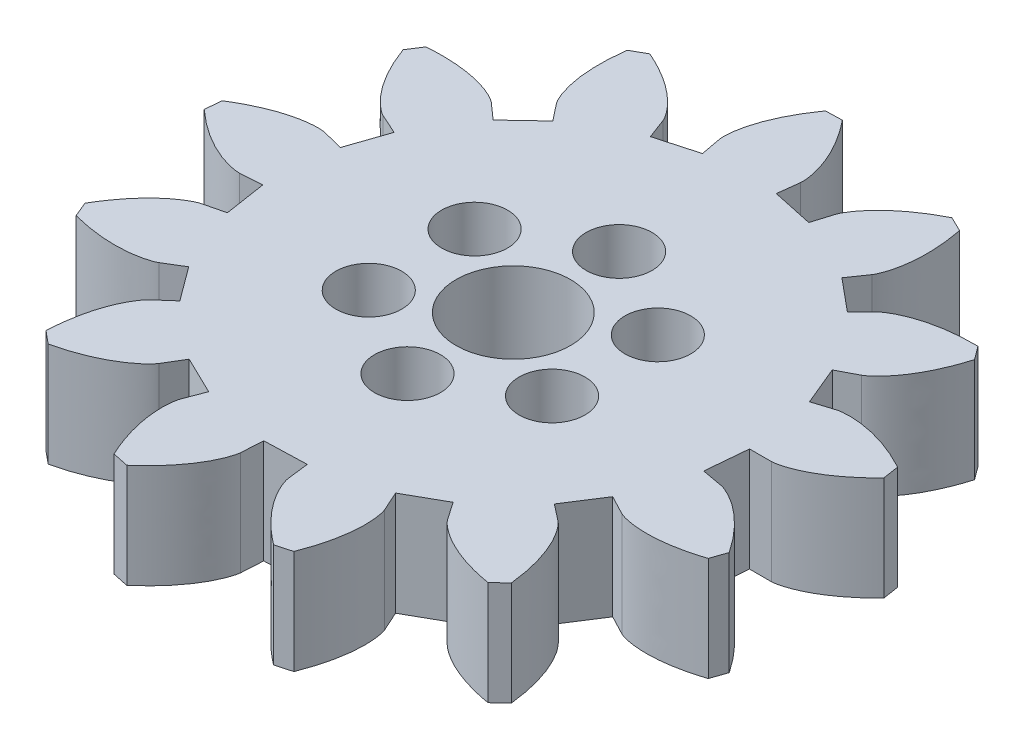
SolidWorks part; units mm, degrees
ref_plane "Front Plane" through (0, 0, 0) normal (0, 0, 1) x (1, 0, 0)
ref_plane "Top Plane" through (0, 0, 0) normal (0, 1, 0) x (1, 0, 0)
ref_plane "Right Plane" through (0, 0, 0) normal (1, 0, 0) x (0, 0, -1)
sketch "Sketch1" plane through (0, 0, 0) normal (0, 1, 0) x (1, 0, 0)
  circle A0 centre (0, 0) radius 8.2743 construction
  circle A1 centre (0, 0) radius 8.2743
  circle A3 centre (-2.6414, -1.525) radius 0.95
  circle A4 centre (-2.6414, -1.525) radius 0.95
  circle A5 centre (0, -3.05) radius 0.95
  circle A6 centre (0, -3.05) radius 0.95
  circle A7 centre (2.6414, -1.525) radius 0.95
  circle A8 centre (2.6414, -1.525) radius 0.95
  circle A9 centre (2.6414, 1.525) radius 0.95
  circle A10 centre (2.6414, 1.525) radius 0.95
  circle A11 centre (0, 3.05) radius 0.95
  circle A12 centre (0, 3.05) radius 0.95
  circle A13 centre (-2.6414, 1.525) radius 0.95
  circle A14 centre (-2.6414, 1.525) radius 0.95
  dimension "D1" = 0
  dimension "D2" = 0
  dimension "D3" = 0
  dimension "D4" = 0
  dimension "D5" = 0
  dimension "D6" = 0
sketch "Sketch2" plane through (0, 0, 0) normal (0, 1, 0) x (1, 0, 0)
  line L0 (6.8098, 0) -> (7.4374, 0)
  line L1 (7.4374, 0) -> (7.4435, 0.0002)
  line L2 (7.4435, 0.0002) -> (7.455, 0.0009)
  line L3 (7.455, 0.0009) -> (7.4719, 0.0023)
  line L4 (7.4719, 0.0023) -> (7.494, 0.0048)
  line L5 (7.494, 0.0048) -> (7.5213, 0.0086)
  line L6 (7.5213, 0.0086) -> (7.5538, 0.0141)
  line L7 (7.5538, 0.0141) -> (7.5915, 0.0214)
  line L8 (7.5915, 0.0214) -> (7.6341, 0.0309)
  line L9 (7.6341, 0.0309) -> (7.6817, 0.0428)
  line L10 (7.6817, 0.0428) -> (7.7341, 0.0575)
  line L11 (7.7341, 0.0575) -> (7.7912, 0.0751)
  line L12 (7.7912, 0.0751) -> (7.8529, 0.096)
  line L13 (7.8529, 0.096) -> (7.9191, 0.1204)
  line L14 (7.9191, 0.1204) -> (7.9895, 0.1486)
  line L15 (7.9895, 0.1486) -> (8.0641, 0.1807)
  line L16 (8.0641, 0.1807) -> (8.1427, 0.2171)
  line L17 (8.1427, 0.2171) -> (8.225, 0.258)
  line L18 (8.225, 0.258) -> (8.311, 0.3036)
  line L19 (8.311, 0.3036) -> (8.4004, 0.3541)
  line L20 (8.4004, 0.3541) -> (8.493, 0.4097)
  line L21 (8.493, 0.4097) -> (8.5886, 0.4707)
  line L22 (8.5886, 0.4707) -> (8.6869, 0.5373)
  line L23 (8.6869, 0.5373) -> (8.7878, 0.6095)
  line L24 (8.7878, 0.6095) -> (8.891, 0.6877)
  line L25 (8.891, 0.6877) -> (8.9962, 0.772)
  line L26 (8.9962, 0.772) -> (9.1033, 0.8626)
  line L27 (9.1033, 0.8626) -> (9.2118, 0.9596)
  line L28 (9.2118, 0.9596) -> (9.3216, 1.0631)
  line L29 (9.3216, 1.0631) -> (9.4324, 1.1733)
  line L30 (9.4324, 1.1733) -> (9.4602, 1.2019)
  line L31 (9.4602, 1.2019) -> (9.4672, 1.2092)
  line L32 (9.4672, 1.2092) -> (9.4689, 1.211)
  line L33 (9.4689, 1.211) -> (9.4692, 1.2112)
  line L34 (9.4692, 1.2112) -> (9.4693, 1.2114)
  line L35 (9.4693, 1.2114) -> (9.3971, 1.6821)
  line L36 (9.3971, 1.6821) -> (9.3969, 1.6823)
  line L37 (9.3969, 1.6823) -> (9.3966, 1.6825)
  line L38 (9.3966, 1.6825) -> (9.3944, 1.6837)
  line L39 (9.3944, 1.6837) -> (9.3856, 1.6885)
  line L40 (9.3856, 1.6885) -> (9.3505, 1.7074)
  line L41 (9.3505, 1.7074) -> (9.2118, 1.7794)
  line L42 (9.2118, 1.7794) -> (9.076, 1.8452)
  line L43 (9.076, 1.8452) -> (8.9434, 1.9052)
  line L44 (8.9434, 1.9052) -> (8.8141, 1.9595)
  line L45 (8.8141, 1.9595) -> (8.6884, 2.0084)
  line L46 (8.6884, 2.0084) -> (8.5666, 2.0521)
  line L47 (8.5666, 2.0521) -> (8.4487, 2.0908)
  line L48 (8.4487, 2.0908) -> (8.3349, 2.1248)
  line L49 (8.3349, 2.1248) -> (8.2254, 2.1544)
  line L50 (8.2254, 2.1544) -> (8.1204, 2.1797)
  line L51 (8.1204, 2.1797) -> (8.02, 2.2011)
  line L52 (8.02, 2.2011) -> (7.9243, 2.2189)
  line L53 (7.9243, 2.2189) -> (7.8335, 2.2332)
  line L54 (7.8335, 2.2332) -> (7.7476, 2.2443)
  line L55 (7.7476, 2.2443) -> (7.6668, 2.2527)
  line L56 (7.6668, 2.2527) -> (7.5912, 2.2584)
  line L57 (7.5912, 2.2584) -> (7.5207, 2.2618)
  line L58 (7.5207, 2.2618) -> (7.4556, 2.2633)
  line L59 (7.4556, 2.2633) -> (7.3958, 2.263)
  line L60 (7.3958, 2.263) -> (7.3415, 2.2613)
  line L61 (7.3415, 2.2613) -> (7.2925, 2.2584)
  line L62 (7.2925, 2.2584) -> (7.2489, 2.2547)
  line L63 (7.2489, 2.2547) -> (7.2109, 2.2504)
  line L64 (7.2109, 2.2504) -> (7.1782, 2.2458)
  line L65 (7.1782, 2.2458) -> (7.151, 2.2413)
  line L66 (7.151, 2.2413) -> (7.1291, 2.237)
  line L67 (7.1291, 2.237) -> (7.1126, 2.2334)
  line L68 (7.1126, 2.2334) -> (7.1015, 2.2306)
  line L69 (7.1015, 2.2306) -> (7.0955, 2.2289)
  line L70 (7.0955, 2.2289) -> (6.4968, 2.0408)
  line L71 (6.4968, 2.0408) -> (6.0298, 3.1647)
  line L72 (6.0298, 3.1647) -> (6.5855, 3.4563)
  line L73 (6.5855, 3.4563) -> (6.5908, 3.4594)
  line L74 (6.5908, 3.4594) -> (6.6007, 3.4653)
  line L75 (6.6007, 3.4653) -> (6.6149, 3.4744)
  line L76 (6.6149, 3.4744) -> (6.6333, 3.4869)
  line L77 (6.6333, 3.4869) -> (6.6558, 3.503)
  line L78 (6.6558, 3.503) -> (6.6821, 3.5229)
  line L79 (6.6821, 3.5229) -> (6.712, 3.5469)
  line L80 (6.712, 3.5469) -> (6.7453, 3.5751)
  line L81 (6.7453, 3.5751) -> (6.7819, 3.6078)
  line L82 (6.7819, 3.6078) -> (6.8215, 3.6451)
  line L83 (6.8215, 3.6451) -> (6.8639, 3.6873)
  line L84 (6.8639, 3.6873) -> (6.9088, 3.7345)
  line L85 (6.9088, 3.7345) -> (6.956, 3.7868)
  line L86 (6.956, 3.7868) -> (7.0053, 3.8445)
  line L87 (7.0053, 3.8445) -> (7.0564, 3.9076)
  line L88 (7.0564, 3.9076) -> (7.1091, 3.9763)
  line L89 (7.1091, 3.9763) -> (7.163, 4.0508)
  line L90 (7.163, 4.0508) -> (7.218, 4.1311)
  line L91 (7.218, 4.1311) -> (7.2736, 4.2174)
  line L92 (7.2736, 4.2174) -> (7.3298, 4.3097)
  line L93 (7.3298, 4.3097) -> (7.3861, 4.4081)
  line L94 (7.3861, 4.4081) -> (7.4422, 4.5127)
  line L95 (7.4422, 4.5127) -> (7.498, 4.6236)
  line L96 (7.498, 4.6236) -> (7.553, 4.7408)
  line L97 (7.553, 4.7408) -> (7.607, 4.8644)
  line L98 (7.607, 4.8644) -> (7.6597, 4.9943)
  line L99 (7.6597, 4.9943) -> (7.7107, 5.1306)
  line L100 (7.7107, 5.1306) -> (7.7598, 5.2733)
  line L101 (7.7598, 5.2733) -> (7.8067, 5.4224)
  line L102 (7.8067, 5.4224) -> (7.8181, 5.4607)
  line L103 (7.8181, 5.4607) -> (7.8209, 5.4703)
  line L104 (7.8209, 5.4703) -> (7.8216, 5.4727)
  line L105 (7.8216, 5.4727) -> (7.8217, 5.473)
  line L106 (7.8217, 5.473) -> (7.8216, 5.4732)
  line L107 (7.8216, 5.4732) -> (7.539, 5.8565)
  line L108 (7.539, 5.8565) -> (7.5387, 5.8566)
  line L109 (7.5387, 5.8566) -> (7.5384, 5.8566)
  line L110 (7.5384, 5.8566) -> (7.5359, 5.8566)
  line L111 (7.5359, 5.8566) -> (7.5259, 5.8568)
  line L112 (7.5259, 5.8568) -> (7.486, 5.8572)
  line L113 (7.486, 5.8572) -> (7.3297, 5.8565)
  line L114 (7.3297, 5.8565) -> (7.1789, 5.8517)
  line L115 (7.1789, 5.8517) -> (7.0336, 5.8432)
  line L116 (7.0336, 5.8432) -> (6.8939, 5.8312)
  line L117 (6.8939, 5.8312) -> (6.7599, 5.8161)
  line L118 (6.7599, 5.8161) -> (6.6317, 5.7981)
  line L119 (6.6317, 5.7981) -> (6.5093, 5.7776)
  line L120 (6.5093, 5.7776) -> (6.3927, 5.7549)
  line L121 (6.3927, 5.7549) -> (6.282, 5.7302)
  line L122 (6.282, 5.7302) -> (6.1773, 5.7038)
  line L123 (6.1773, 5.7038) -> (6.0784, 5.6761)
  line L124 (6.0784, 5.6761) -> (5.9855, 5.6473)
  line L125 (5.9855, 5.6473) -> (5.8984, 5.6178)
  line L126 (5.8984, 5.6178) -> (5.8172, 5.5878)
  line L127 (5.8172, 5.5878) -> (5.7418, 5.5576)
  line L128 (5.7418, 5.5576) -> (5.6721, 5.5275)
  line L129 (5.6721, 5.5275) -> (5.6082, 5.4978)
  line L130 (5.6082, 5.4978) -> (5.5498, 5.4688)
  line L131 (5.5498, 5.4688) -> (5.497, 5.4408)
  line L132 (5.497, 5.4408) -> (5.4497, 5.414)
  line L133 (5.4497, 5.414) -> (5.4076, 5.3887)
  line L134 (5.4076, 5.3887) -> (5.3708, 5.3652)
  line L135 (5.3708, 5.3652) -> (5.3391, 5.3437)
  line L136 (5.3391, 5.3437) -> (5.3123, 5.3245)
  line L137 (5.3123, 5.3245) -> (5.2903, 5.3078)
  line L138 (5.2903, 5.3078) -> (5.2729, 5.2939)
  line L139 (5.2729, 5.2939) -> (5.26, 5.283)
  line L140 (5.26, 5.283) -> (5.2514, 5.2753)
  line L141 (5.2514, 5.2753) -> (5.247, 5.2711)
  line L142 (5.247, 5.2711) -> (4.8042, 4.8263)
  line L143 (4.8042, 4.8263) -> (3.8684, 5.6043)
  line L144 (3.8684, 5.6043) -> (4.2249, 6.1208)
  line L145 (4.2249, 6.1208) -> (4.2282, 6.126)
  line L146 (4.2282, 6.126) -> (4.2342, 6.1359)
  line L147 (4.2342, 6.1359) -> (4.2426, 6.1505)
  line L148 (4.2426, 6.1505) -> (4.2531, 6.1702)
  line L149 (4.2531, 6.1702) -> (4.2655, 6.1948)
  line L150 (4.2655, 6.1948) -> (4.2795, 6.2247)
  line L151 (4.2795, 6.2247) -> (4.2948, 6.2598)
  line L152 (4.2948, 6.2598) -> (4.3112, 6.3003)
  line L153 (4.3112, 6.3003) -> (4.3284, 6.3462)
  line L154 (4.3284, 6.3462) -> (4.3462, 6.3977)
  line L155 (4.3462, 6.3977) -> (4.3641, 6.4547)
  line L156 (4.3641, 6.4547) -> (4.3819, 6.5174)
  line L157 (4.3819, 6.5174) -> (4.3994, 6.5857)
  line L158 (4.3994, 6.5857) -> (4.4163, 6.6596)
  line L159 (4.4163, 6.6596) -> (4.4322, 6.7393)
  line L160 (4.4322, 6.7393) -> (4.4469, 6.8246)
  line L161 (4.4469, 6.8246) -> (4.46, 6.9156)
  line L162 (4.46, 6.9156) -> (4.4714, 7.0123)
  line L163 (4.4714, 7.0123) -> (4.4806, 7.1145)
  line L164 (4.4806, 7.1145) -> (4.4874, 7.2223)
  line L165 (4.4874, 7.2223) -> (4.4915, 7.3356)
  line L166 (4.4915, 7.3356) -> (4.4926, 7.4544)
  line L167 (4.4926, 7.4544) -> (4.4904, 7.5785)
  line L168 (4.4904, 7.5785) -> (4.4847, 7.7078)
  line L169 (4.4847, 7.7078) -> (4.4751, 7.8423)
  line L170 (4.4751, 7.8423) -> (4.4613, 7.9819)
  line L171 (4.4613, 7.9819) -> (4.4432, 8.1263)
  line L172 (4.4432, 8.1263) -> (4.4204, 8.2755)
  line L173 (4.4204, 8.2755) -> (4.3926, 8.4293)
  line L174 (4.3926, 8.4293) -> (4.3849, 8.4684)
  line L175 (4.3849, 8.4684) -> (4.3829, 8.4782)
  line L176 (4.3829, 8.4782) -> (4.3824, 8.4807)
  line L177 (4.3824, 8.4807) -> (4.3823, 8.481)
  line L178 (4.3823, 8.481) -> (4.3822, 8.4812)
  line L179 (4.3822, 8.4812) -> (3.9538, 8.6892)
  line L180 (3.9538, 8.6892) -> (3.9535, 8.6892)
  line L181 (3.9535, 8.6892) -> (3.9533, 8.689)
  line L182 (3.9533, 8.689) -> (3.951, 8.6879)
  line L183 (3.951, 8.6879) -> (3.9421, 8.6834)
  line L184 (3.9421, 8.6834) -> (3.9065, 8.6652)
  line L185 (3.9065, 8.6652) -> (3.7685, 8.5919)
  line L186 (3.7685, 8.5919) -> (3.6371, 8.5176)
  line L187 (3.6371, 8.5176) -> (3.5125, 8.4425)
  line L188 (3.5125, 8.4425) -> (3.3943, 8.367)
  line L189 (3.3943, 8.367) -> (3.2827, 8.2914)
  line L190 (3.2827, 8.2914) -> (3.1775, 8.2159)
  line L191 (3.1775, 8.2159) -> (3.0787, 8.1408)
  line L192 (3.0787, 8.1408) -> (2.986, 8.0665)
  line L193 (2.986, 8.0665) -> (2.8995, 7.9932)
  line L194 (2.8995, 7.9932) -> (2.819, 7.9212)
  line L195 (2.819, 7.9212) -> (2.7444, 7.8507)
  line L196 (2.7444, 7.8507) -> (2.6754, 7.782)
  line L197 (2.6754, 7.782) -> (2.6121, 7.7154)
  line L198 (2.6121, 7.7154) -> (2.5541, 7.6511)
  line L199 (2.5541, 7.6511) -> (2.5013, 7.5893)
  line L200 (2.5013, 7.5893) -> (2.4537, 7.5303)
  line L201 (2.4537, 7.5303) -> (2.4108, 7.4743)
  line L202 (2.4108, 7.4743) -> (2.3726, 7.4215)
  line L203 (2.3726, 7.4215) -> (2.3389, 7.3722)
  line L204 (2.3389, 7.3722) -> (2.3094, 7.3265)
  line L205 (2.3094, 7.3265) -> (2.284, 7.2845)
  line L206 (2.284, 7.2845) -> (2.2623, 7.2466)
  line L207 (2.2623, 7.2466) -> (2.2442, 7.2128)
  line L208 (2.2442, 7.2128) -> (2.2294, 7.1833)
  line L209 (2.2294, 7.1833) -> (2.2177, 7.1583)
  line L210 (2.2177, 7.1583) -> (2.2088, 7.1379)
  line L211 (2.2088, 7.1379) -> (2.2024, 7.1223)
  line L212 (2.2024, 7.1223) -> (2.1984, 7.1115)
  line L213 (2.1984, 7.1115) -> (2.1964, 7.1057)
  line L214 (2.1964, 7.1057) -> (2.011, 6.5061)
  line L215 (2.011, 6.5061) -> (0.8208, 6.7601)
  line L216 (0.8208, 6.7601) -> (0.8965, 7.3831)
  line L217 (0.8965, 7.3831) -> (0.897, 7.3893)
  line L218 (0.897, 7.3893) -> (0.8977, 7.4008)
  line L219 (0.8977, 7.4008) -> (0.8983, 7.4177)
  line L220 (0.8983, 7.4177) -> (0.8985, 7.4399)
  line L221 (0.8985, 7.4399) -> (0.898, 7.4675)
  line L222 (0.898, 7.4675) -> (0.8965, 7.5005)
  line L223 (0.8965, 7.5005) -> (0.8938, 7.5387)
  line L224 (0.8938, 7.5387) -> (0.8895, 7.5822)
  line L225 (0.8895, 7.5822) -> (0.8834, 7.6309)
  line L226 (0.8834, 7.6309) -> (0.8752, 7.6846)
  line L227 (0.8752, 7.6846) -> (0.8645, 7.7435)
  line L228 (0.8645, 7.7435) -> (0.8512, 7.8072)
  line L229 (0.8512, 7.8072) -> (0.835, 7.8758)
  line L230 (0.835, 7.8758) -> (0.8156, 7.9492)
  line L231 (0.8156, 7.9492) -> (0.7926, 8.0271)
  line L232 (0.7926, 8.0271) -> (0.766, 8.1095)
  line L233 (0.766, 8.1095) -> (0.7353, 8.1962)
  line L234 (0.7353, 8.1962) -> (0.7004, 8.287)
  line L235 (0.7004, 8.287) -> (0.6611, 8.3818)
  line L236 (0.6611, 8.3818) -> (0.617, 8.4804)
  line L237 (0.617, 8.4804) -> (0.568, 8.5827)
  line L238 (0.568, 8.5827) -> (0.5138, 8.6883)
  line L239 (0.5138, 8.6883) -> (0.4542, 8.7972)
  line L240 (0.4542, 8.7972) -> (0.389, 8.9091)
  line L241 (0.389, 8.9091) -> (0.318, 9.0237)
  line L242 (0.318, 9.0237) -> (0.241, 9.1409)
  line L243 (0.241, 9.1409) -> (0.1578, 9.2603)
  line L244 (0.1578, 9.2603) -> (0.0682, 9.3818)
  line L245 (0.0682, 9.3818) -> (-0.0278, 9.5051)
  line L246 (-0.0278, 9.5051) -> (-0.0529, 9.5361)
  line L247 (-0.0529, 9.5361) -> (-0.0592, 9.5439)
  line L248 (-0.0592, 9.5439) -> (-0.0608, 9.5459)
  line L249 (-0.0608, 9.5459) -> (-0.061, 9.5461)
  line L250 (-0.061, 9.5461) -> (-0.0612, 9.5462)
  line L251 (-0.0612, 9.5462) -> (-0.5372, 9.5313)
  line L252 (-0.5372, 9.5313) -> (-0.5374, 9.5312)
  line L253 (-0.5374, 9.5312) -> (-0.5375, 9.5309)
  line L254 (-0.5375, 9.5309) -> (-0.539, 9.5289)
  line L255 (-0.539, 9.5289) -> (-0.5448, 9.5207)
  line L256 (-0.5448, 9.5207) -> (-0.5679, 9.4881)
  line L257 (-0.5679, 9.4881) -> (-0.656, 9.3591)
  line L258 (-0.656, 9.3591) -> (-0.7378, 9.2322)
  line L259 (-0.7378, 9.2322) -> (-0.8133, 9.1078)
  line L260 (-0.8133, 9.1078) -> (-0.8828, 8.986)
  line L261 (-0.8828, 8.986) -> (-0.9465, 8.8672)
  line L262 (-0.9465, 8.8672) -> (-1.0046, 8.7515)
  line L263 (-1.0046, 8.7515) -> (-1.0572, 8.6391)
  line L264 (-1.0572, 8.6391) -> (-1.1047, 8.5302)
  line L265 (-1.1047, 8.5302) -> (-1.1472, 8.4251)
  line L266 (-1.1472, 8.4251) -> (-1.185, 8.3239)
  line L267 (-1.185, 8.3239) -> (-1.2184, 8.2268)
  line L268 (-1.2184, 8.2268) -> (-1.2475, 8.134)
  line L269 (-1.2475, 8.134) -> (-1.2727, 8.0455)
  line L270 (-1.2727, 8.0455) -> (-1.2941, 7.9616)
  line L271 (-1.2941, 7.9616) -> (-1.3121, 7.8824)
  line L272 (-1.3121, 7.8824) -> (-1.3269, 7.808)
  line L273 (-1.3269, 7.808) -> (-1.3388, 7.7385)
  line L274 (-1.3388, 7.7385) -> (-1.3481, 7.6741)
  line L275 (-1.3481, 7.6741) -> (-1.355, 7.6147)
  line L276 (-1.355, 7.6147) -> (-1.3599, 7.5605)
  line L277 (-1.3599, 7.5605) -> (-1.3629, 7.5115)
  line L278 (-1.3629, 7.5115) -> (-1.3645, 7.4679)
  line L279 (-1.3645, 7.4679) -> (-1.3648, 7.4295)
  line L280 (-1.3648, 7.4295) -> (-1.3642, 7.3966)
  line L281 (-1.3642, 7.3966) -> (-1.363, 7.369)
  line L282 (-1.363, 7.369) -> (-1.3614, 7.3468)
  line L283 (-1.3614, 7.3468) -> (-1.3597, 7.33)
  line L284 (-1.3597, 7.33) -> (-1.3583, 7.3186)
  line L285 (-1.3583, 7.3186) -> (-1.3574, 7.3125)
  line L286 (-1.3574, 7.3125) -> (-1.2429, 6.6954)
  line L287 (-1.2429, 6.6954) -> (-2.4148, 6.3673)
  line L288 (-2.4148, 6.3673) -> (-2.6373, 6.9541)
  line L289 (-2.6373, 6.9541) -> (-2.6397, 6.9598)
  line L290 (-2.6397, 6.9598) -> (-2.6444, 6.9703)
  line L291 (-2.6444, 6.9703) -> (-2.6517, 6.9855)
  line L292 (-2.6517, 6.9855) -> (-2.6619, 7.0053)
  line L293 (-2.6619, 7.0053) -> (-2.6752, 7.0295)
  line L294 (-2.6752, 7.0295) -> (-2.6918, 7.058)
  line L295 (-2.6918, 7.058) -> (-2.712, 7.0906)
  line L296 (-2.712, 7.0906) -> (-2.736, 7.1271)
  line L297 (-2.736, 7.1271) -> (-2.764, 7.1673)
  line L298 (-2.764, 7.1673) -> (-2.7963, 7.2111)
  line L299 (-2.7963, 7.2111) -> (-2.8331, 7.2583)
  line L300 (-2.8331, 7.2583) -> (-2.8745, 7.3086)
  line L301 (-2.8745, 7.3086) -> (-2.9207, 7.3618)
  line L302 (-2.9207, 7.3618) -> (-2.972, 7.4176)
  line L303 (-2.972, 7.4176) -> (-3.0285, 7.476)
  line L304 (-3.0285, 7.476) -> (-3.0904, 7.5365)
  line L305 (-3.0904, 7.5365) -> (-3.1578, 7.5991)
  line L306 (-3.1578, 7.5991) -> (-3.2309, 7.6633)
  line L307 (-3.2309, 7.6633) -> (-3.3099, 7.729)
  line L308 (-3.3099, 7.729) -> (-3.3947, 7.7958)
  line L309 (-3.3947, 7.7958) -> (-3.4857, 7.8635)
  line L310 (-3.4857, 7.8635) -> (-3.5828, 7.9319)
  line L311 (-3.5828, 7.9319) -> (-3.6861, 8.0006)
  line L312 (-3.6861, 8.0006) -> (-3.7958, 8.0694)
  line L313 (-3.7958, 8.0694) -> (-3.912, 8.1379)
  line L314 (-3.912, 8.1379) -> (-4.0346, 8.2058)
  line L315 (-4.0346, 8.2058) -> (-4.1638, 8.2729)
  line L316 (-4.1638, 8.2729) -> (-4.2995, 8.3389)
  line L317 (-4.2995, 8.3389) -> (-4.4419, 8.4034)
  line L318 (-4.4419, 8.4034) -> (-4.4785, 8.4193)
  line L319 (-4.4785, 8.4193) -> (-4.4877, 8.4232)
  line L320 (-4.4877, 8.4232) -> (-4.49, 8.4242)
  line L321 (-4.49, 8.4242) -> (-4.4903, 8.4243)
  line L322 (-4.4903, 8.4243) -> (-4.4905, 8.4243)
  line L323 (-4.4905, 8.4243) -> (-4.9051, 8.1899)
  line L324 (-4.9051, 8.1899) -> (-4.9052, 8.1897)
  line L325 (-4.9052, 8.1897) -> (-4.9052, 8.1894)
  line L326 (-4.9052, 8.1894) -> (-4.9056, 8.1869)
  line L327 (-4.9056, 8.1869) -> (-4.9069, 8.177)
  line L328 (-4.9069, 8.177) -> (-4.9122, 8.1374)
  line L329 (-4.9122, 8.1374) -> (-4.9303, 7.9822)
  line L330 (-4.9303, 7.9822) -> (-4.9437, 7.8319)
  line L331 (-4.9437, 7.8319) -> (-4.9528, 7.6866)
  line L332 (-4.9528, 7.6866) -> (-4.9577, 7.5465)
  line L333 (-4.9577, 7.5465) -> (-4.9589, 7.4116)
  line L334 (-4.9589, 7.4116) -> (-4.9565, 7.2822)
  line L335 (-4.9565, 7.2822) -> (-4.9509, 7.1582)
  line L336 (-4.9509, 7.1582) -> (-4.9424, 7.0398)
  line L337 (-4.9424, 7.0398) -> (-4.9312, 6.9269)
  line L338 (-4.9312, 6.9269) -> (-4.9176, 6.8197)
  line L339 (-4.9176, 6.8197) -> (-4.902, 6.7183)
  line L340 (-4.902, 6.7183) -> (-4.8847, 6.6225)
  line L341 (-4.8847, 6.6225) -> (-4.8658, 6.5325)
  line L342 (-4.8658, 6.5325) -> (-4.8458, 6.4483)
  line L343 (-4.8458, 6.4483) -> (-4.825, 6.3698)
  line L344 (-4.825, 6.3698) -> (-4.8035, 6.297)
  line L345 (-4.8035, 6.297) -> (-4.7818, 6.23)
  line L346 (-4.7818, 6.23) -> (-4.76, 6.1686)
  line L347 (-4.76, 6.1686) -> (-4.7385, 6.1128)
  line L348 (-4.7385, 6.1128) -> (-4.7176, 6.0625)
  line L349 (-4.7176, 6.0625) -> (-4.6976, 6.0177)
  line L350 (-4.6976, 6.0177) -> (-4.6787, 5.9784)
  line L351 (-4.6787, 5.9784) -> (-4.6612, 5.9443)
  line L352 (-4.6612, 5.9443) -> (-4.6453, 5.9154)
  line L353 (-4.6453, 5.9154) -> (-4.6314, 5.8915)
  line L354 (-4.6314, 5.8915) -> (-4.6197, 5.8726)
  line L355 (-4.6197, 5.8726) -> (-4.6104, 5.8585)
  line L356 (-4.6104, 5.8585) -> (-4.6038, 5.849)
  line L357 (-4.6038, 5.849) -> (-4.6002, 5.8441)
  line L358 (-4.6002, 5.8441) -> (-4.212, 5.3509)
  line L359 (-4.212, 5.3509) -> (-5.0972, 4.5157)
  line L360 (-5.0972, 4.5157) -> (-5.567, 4.9319)
  line L361 (-5.567, 4.9319) -> (-5.5717, 4.9358)
  line L362 (-5.5717, 4.9358) -> (-5.5808, 4.9429)
  line L363 (-5.5808, 4.9429) -> (-5.5943, 4.953)
  line L364 (-5.5943, 4.953) -> (-5.6125, 4.9658)
  line L365 (-5.6125, 4.9658) -> (-5.6355, 4.9811)
  line L366 (-5.6355, 4.9811) -> (-5.6635, 4.9986)
  line L367 (-5.6635, 4.9986) -> (-5.6965, 5.0181)
  line L368 (-5.6965, 5.0181) -> (-5.7347, 5.0392)
  line L369 (-5.7347, 5.0392) -> (-5.7782, 5.0618)
  line L370 (-5.7782, 5.0618) -> (-5.8272, 5.0856)
  line L371 (-5.8272, 5.0856) -> (-5.8816, 5.1103)
  line L372 (-5.8816, 5.1103) -> (-5.9417, 5.1356)
  line L373 (-5.9417, 5.1356) -> (-6.0074, 5.1612)
  line L374 (-6.0074, 5.1612) -> (-6.0787, 5.1868)
  line L375 (-6.0787, 5.1868) -> (-6.1559, 5.2122)
  line L376 (-6.1559, 5.2122) -> (-6.2388, 5.2371)
  line L377 (-6.2388, 5.2371) -> (-6.3276, 5.2611)
  line L378 (-6.3276, 5.2611) -> (-6.4222, 5.284)
  line L379 (-6.4222, 5.284) -> (-6.5226, 5.3055)
  line L380 (-6.5226, 5.3055) -> (-6.6288, 5.3252)
  line L381 (-6.6288, 5.3252) -> (-6.7408, 5.3429)
  line L382 (-6.7408, 5.3429) -> (-6.8585, 5.3584)
  line L383 (-6.8585, 5.3584) -> (-6.982, 5.3712)
  line L384 (-6.982, 5.3712) -> (-7.1111, 5.381)
  line L385 (-7.1111, 5.381) -> (-7.2457, 5.3877)
  line L386 (-7.2457, 5.3877) -> (-7.3859, 5.3909)
  line L387 (-7.3859, 5.3909) -> (-7.5315, 5.3903)
  line L388 (-7.5315, 5.3903) -> (-7.6823, 5.3856)
  line L389 (-7.6823, 5.3856) -> (-7.8383, 5.3766)
  line L390 (-7.8383, 5.3766) -> (-7.8781, 5.3736)
  line L391 (-7.8781, 5.3736) -> (-7.8881, 5.3729)
  line L392 (-7.8881, 5.3729) -> (-7.8906, 5.3727)
  line L393 (-7.8906, 5.3727) -> (-7.8909, 5.3726)
  line L394 (-7.8909, 5.3726) -> (-7.8912, 5.3725)
  line L395 (-7.8912, 5.3725) -> (-8.1493, 4.9723)
  line L396 (-8.1493, 4.9723) -> (-8.1493, 4.9721)
  line L397 (-8.1493, 4.9721) -> (-8.1492, 4.9718)
  line L398 (-8.1492, 4.9718) -> (-8.1483, 4.9694)
  line L399 (-8.1483, 4.9694) -> (-8.1449, 4.96)
  line L400 (-8.1449, 4.96) -> (-8.1312, 4.9225)
  line L401 (-8.1312, 4.9225) -> (-8.0751, 4.7767)
  line L402 (-8.0751, 4.7767) -> (-8.0171, 4.6373)
  line L403 (-8.0171, 4.6373) -> (-7.9576, 4.5045)
  line L404 (-7.9576, 4.5045) -> (-7.8969, 4.3781)
  line L405 (-7.8969, 4.3781) -> (-7.8352, 4.2582)
  line L406 (-7.8352, 4.2582) -> (-7.773, 4.1447)
  line L407 (-7.773, 4.1447) -> (-7.7104, 4.0375)
  line L408 (-7.7104, 4.0375) -> (-7.6478, 3.9366)
  line L409 (-7.6478, 3.9366) -> (-7.5854, 3.8419)
  line L410 (-7.5854, 3.8419) -> (-7.5236, 3.7533)
  line L411 (-7.5236, 3.7533) -> (-7.4627, 3.6707)
  line L412 (-7.4627, 3.6707) -> (-7.4028, 3.5939)
  line L413 (-7.4028, 3.5939) -> (-7.3443, 3.523)
  line L414 (-7.3443, 3.523) -> (-7.2874, 3.4577)
  line L415 (-7.2874, 3.4577) -> (-7.2325, 3.3979)
  line L416 (-7.2325, 3.3979) -> (-7.1797, 3.3434)
  line L417 (-7.1797, 3.3434) -> (-7.1292, 3.2942)
  line L418 (-7.1292, 3.2942) -> (-7.0814, 3.2499)
  line L419 (-7.0814, 3.2499) -> (-7.0365, 3.2105)
  line L420 (-7.0365, 3.2105) -> (-6.9947, 3.1757)
  line L421 (-6.9947, 3.1757) -> (-6.9561, 3.1454)
  line L422 (-6.9561, 3.1454) -> (-6.9211, 3.1193)
  line L423 (-6.9211, 3.1193) -> (-6.8897, 3.0972)
  line L424 (-6.8897, 3.0972) -> (-6.8622, 3.079)
  line L425 (-6.8622, 3.079) -> (-6.8388, 3.0643)
  line L426 (-6.8388, 3.0643) -> (-6.8197, 3.0531)
  line L427 (-6.8197, 3.0531) -> (-6.8049, 3.0449)
  line L428 (-6.8049, 3.0449) -> (-6.7947, 3.0395)
  line L429 (-6.7947, 3.0395) -> (-6.7891, 3.0368)
  line L430 (-6.7891, 3.0368) -> (-6.2162, 2.7806)
  line L431 (-6.2162, 2.7806) -> (-6.6119, 1.6297)
  line L432 (-6.6119, 1.6297) -> (-7.2213, 1.7799)
  line L433 (-7.2213, 1.7799) -> (-7.2273, 1.7811)
  line L434 (-7.2273, 1.7811) -> (-7.2386, 1.7832)
  line L435 (-7.2386, 1.7832) -> (-7.2553, 1.7859)
  line L436 (-7.2553, 1.7859) -> (-7.2774, 1.7887)
  line L437 (-7.2774, 1.7887) -> (-7.3048, 1.7916)
  line L438 (-7.3048, 1.7916) -> (-7.3377, 1.7941)
  line L439 (-7.3377, 1.7941) -> (-7.376, 1.796)
  line L440 (-7.376, 1.796) -> (-7.4197, 1.797)
  line L441 (-7.4197, 1.797) -> (-7.4687, 1.7968)
  line L442 (-7.4687, 1.7968) -> (-7.5231, 1.7951)
  line L443 (-7.5231, 1.7951) -> (-7.5828, 1.7916)
  line L444 (-7.5828, 1.7916) -> (-7.6477, 1.7861)
  line L445 (-7.6477, 1.7861) -> (-7.7178, 1.7782)
  line L446 (-7.7178, 1.7782) -> (-7.7929, 1.7678)
  line L447 (-7.7929, 1.7678) -> (-7.873, 1.7544)
  line L448 (-7.873, 1.7544) -> (-7.958, 1.7379)
  line L449 (-7.958, 1.7379) -> (-8.0478, 1.7179)
  line L450 (-8.0478, 1.7179) -> (-8.1421, 1.6942)
  line L451 (-8.1421, 1.6942) -> (-8.241, 1.6666)
  line L452 (-8.241, 1.6666) -> (-8.3442, 1.6347)
  line L453 (-8.3442, 1.6347) -> (-8.4517, 1.5984)
  line L454 (-8.4517, 1.5984) -> (-8.5631, 1.5573)
  line L455 (-8.5631, 1.5573) -> (-8.6783, 1.5112)
  line L456 (-8.6783, 1.5112) -> (-8.7972, 1.46)
  line L457 (-8.7972, 1.46) -> (-8.9196, 1.4033)
  line L458 (-8.9196, 1.4033) -> (-9.0452, 1.341)
  line L459 (-9.0452, 1.341) -> (-9.1738, 1.2728)
  line L460 (-9.1738, 1.2728) -> (-9.3052, 1.1986)
  line L461 (-9.3052, 1.1986) -> (-9.4391, 1.1181)
  line L462 (-9.4391, 1.1181) -> (-9.473, 1.097)
  line L463 (-9.473, 1.097) -> (-9.4815, 1.0916)
  line L464 (-9.4815, 1.0916) -> (-9.4836, 1.0903)
  line L465 (-9.4836, 1.0903) -> (-9.4839, 1.0901)
  line L466 (-9.4839, 1.0901) -> (-9.484, 1.0899)
  line L467 (-9.484, 1.0899) -> (-9.5266, 0.6156)
  line L468 (-9.5266, 0.6156) -> (-9.5265, 0.6154)
  line L469 (-9.5265, 0.6154) -> (-9.5262, 0.6152)
  line L470 (-9.5262, 0.6152) -> (-9.5244, 0.6135)
  line L471 (-9.5244, 0.6135) -> (-9.517, 0.6067)
  line L472 (-9.517, 0.6067) -> (-9.4874, 0.5799)
  line L473 (-9.4874, 0.5799) -> (-9.3699, 0.4769)
  line L474 (-9.3699, 0.4769) -> (-9.2538, 0.3804)
  line L475 (-9.2538, 0.3804) -> (-9.1394, 0.2904)
  line L476 (-9.1394, 0.2904) -> (-9.0269, 0.2068)
  line L477 (-9.0269, 0.2068) -> (-8.9166, 0.1292)
  line L478 (-8.9166, 0.1292) -> (-8.8087, 0.0576)
  line L479 (-8.8087, 0.0576) -> (-8.7035, -0.0082)
  line L480 (-8.7035, -0.0082) -> (-8.6012, -0.0684)
  line L481 (-8.6012, -0.0684) -> (-8.502, -0.1233)
  line L482 (-8.502, -0.1233) -> (-8.4061, -0.1731)
  line L483 (-8.4061, -0.1731) -> (-8.3137, -0.2179)
  line L484 (-8.3137, -0.2179) -> (-8.225, -0.258)
  line L485 (-8.225, -0.258) -> (-8.1403, -0.2936)
  line L486 (-8.1403, -0.2936) -> (-8.0596, -0.325)
  line L487 (-8.0596, -0.325) -> (-7.9831, -0.3524)
  line L488 (-7.9831, -0.3524) -> (-7.911, -0.3761)
  line L489 (-7.911, -0.3761) -> (-7.8435, -0.3963)
  line L490 (-7.8435, -0.3963) -> (-7.7806, -0.4133)
  line L491 (-7.7806, -0.4133) -> (-7.7225, -0.4273)
  line L492 (-7.7225, -0.4273) -> (-7.6693, -0.4386)
  line L493 (-7.6693, -0.4386) -> (-7.6211, -0.4476)
  line L494 (-7.6211, -0.4476) -> (-7.5779, -0.4544)
  line L495 (-7.5779, -0.4544) -> (-7.5399, -0.4593)
  line L496 (-7.5399, -0.4593) -> (-7.5071, -0.4627)
  line L497 (-7.5071, -0.4627) -> (-7.4795, -0.4648)
  line L498 (-7.4795, -0.4648) -> (-7.4573, -0.4659)
  line L499 (-7.4573, -0.4659) -> (-7.4404, -0.4663)
  line L500 (-7.4404, -0.4663) -> (-7.4289, -0.4662)
  line L501 (-7.4289, -0.4662) -> (-7.4228, -0.4661)
  line L502 (-7.4228, -0.4661) -> (-6.7964, -0.4267)
  line L503 (-6.7964, -0.4267) -> (-6.6119, -1.6297)
  line L504 (-6.6119, -1.6297) -> (-7.2213, -1.7799)
  line L505 (-7.2213, -1.7799) -> (-7.2272, -1.7816)
  line L506 (-7.2272, -1.7816) -> (-7.2382, -1.785)
  line L507 (-7.2382, -1.785) -> (-7.2542, -1.7904)
  line L508 (-7.2542, -1.7904) -> (-7.2751, -1.7981)
  line L509 (-7.2751, -1.7981) -> (-7.3007, -1.8084)
  line L510 (-7.3007, -1.8084) -> (-7.331, -1.8214)
  line L511 (-7.331, -1.8214) -> (-7.3658, -1.8375)
  line L512 (-7.3658, -1.8375) -> (-7.4049, -1.857)
  line L513 (-7.4049, -1.857) -> (-7.4482, -1.8799)
  line L514 (-7.4482, -1.8799) -> (-7.4956, -1.9067)
  line L515 (-7.4956, -1.9067) -> (-7.5468, -1.9375)
  line L516 (-7.5468, -1.9375) -> (-7.6017, -1.9726)
  line L517 (-7.6017, -1.9726) -> (-7.6601, -2.0121)
  line L518 (-7.6601, -2.0121) -> (-7.7218, -2.0563)
  line L519 (-7.7218, -2.0563) -> (-7.7865, -2.1053)
  line L520 (-7.7865, -2.1053) -> (-7.8541, -2.1595)
  line L521 (-7.8541, -2.1595) -> (-7.9243, -2.2189)
  line L522 (-7.9243, -2.2189) -> (-7.9969, -2.2837)
  line L523 (-7.9969, -2.2837) -> (-8.0716, -2.3541)
  line L524 (-8.0716, -2.3541) -> (-8.1481, -2.4303)
  line L525 (-8.1481, -2.4303) -> (-8.2264, -2.5124)
  line L526 (-8.2264, -2.5124) -> (-8.3059, -2.6006)
  line L527 (-8.3059, -2.6006) -> (-8.3866, -2.6949)
  line L528 (-8.3866, -2.6949) -> (-8.4681, -2.7955)
  line L529 (-8.4681, -2.7955) -> (-8.5501, -2.9026)
  line L530 (-8.5501, -2.9026) -> (-8.6323, -3.0161)
  line L531 (-8.6323, -3.0161) -> (-8.7145, -3.1362)
  line L532 (-8.7145, -3.1362) -> (-8.7963, -3.263)
  line L533 (-8.7963, -3.263) -> (-8.8775, -3.3966)
  line L534 (-8.8775, -3.3966) -> (-8.8977, -3.431)
  line L535 (-8.8977, -3.431) -> (-8.9027, -3.4397)
  line L536 (-8.9027, -3.4397) -> (-8.904, -3.4418)
  line L537 (-8.904, -3.4418) -> (-8.9041, -3.4421)
  line L538 (-8.9041, -3.4421) -> (-8.9042, -3.4423)
  line L539 (-8.9042, -3.4423) -> (-8.7214, -3.8821)
  line L540 (-8.7214, -3.8821) -> (-8.7213, -3.8822)
  line L541 (-8.7213, -3.8822) -> (-8.7209, -3.8823)
  line L542 (-8.7209, -3.8823) -> (-8.7185, -3.883)
  line L543 (-8.7185, -3.883) -> (-8.7088, -3.8855)
  line L544 (-8.7088, -3.8855) -> (-8.6702, -3.8955)
  line L545 (-8.6702, -3.8955) -> (-8.5183, -3.9322)
  line L546 (-8.5183, -3.9322) -> (-8.3707, -3.9636)
  line L547 (-8.3707, -3.9636) -> (-8.2275, -3.9901)
  line L548 (-8.2275, -3.9901) -> (-8.089, -4.0119)
  line L549 (-8.089, -4.0119) -> (-7.9553, -4.0293)
  line L550 (-7.9553, -4.0293) -> (-7.8265, -4.0426)
  line L551 (-7.8265, -4.0426) -> (-7.7028, -4.052)
  line L552 (-7.7028, -4.052) -> (-7.5842, -4.0578)
  line L553 (-7.5842, -4.0578) -> (-7.4708, -4.0603)
  line L554 (-7.4708, -4.0603) -> (-7.3628, -4.0597)
  line L555 (-7.3628, -4.0597) -> (-7.2602, -4.0565)
  line L556 (-7.2602, -4.0565) -> (-7.163, -4.0508)
  line L557 (-7.163, -4.0508) -> (-7.0714, -4.0429)
  line L558 (-7.0714, -4.0429) -> (-6.9854, -4.0332)
  line L559 (-6.9854, -4.0332) -> (-6.9049, -4.022)
  line L560 (-6.9049, -4.022) -> (-6.8301, -4.0095)
  line L561 (-6.8301, -4.0095) -> (-6.7609, -3.9959)
  line L562 (-6.7609, -3.9959) -> (-6.6973, -3.9818)
  line L563 (-6.6973, -3.9818) -> (-6.6394, -3.9672)
  line L564 (-6.6394, -3.9672) -> (-6.587, -3.9525)
  line L565 (-6.587, -3.9525) -> (-6.5401, -3.938)
  line L566 (-6.5401, -3.938) -> (-6.4987, -3.924)
  line L567 (-6.4987, -3.924) -> (-6.4628, -3.9107)
  line L568 (-6.4628, -3.9107) -> (-6.4322, -3.8984)
  line L569 (-6.4322, -3.8984) -> (-6.4068, -3.8875)
  line L570 (-6.4068, -3.8875) -> (-6.3866, -3.8781)
  line L571 (-6.3866, -3.8781) -> (-6.3715, -3.8706)
  line L572 (-6.3715, -3.8706) -> (-6.3613, -3.8652)
  line L573 (-6.3613, -3.8652) -> (-6.3559, -3.8622)
  line L574 (-6.3559, -3.8622) -> (-5.8196, -3.5363)
  line L575 (-5.8196, -3.5363) -> (-5.0972, -4.5157)
  line L576 (-5.0972, -4.5157) -> (-5.5669, -4.9319)
  line L577 (-5.5669, -4.9319) -> (-5.5714, -4.9361)
  line L578 (-5.5714, -4.9361) -> (-5.5796, -4.9443)
  line L579 (-5.5796, -4.9443) -> (-5.5912, -4.9565)
  line L580 (-5.5912, -4.9565) -> (-5.6061, -4.973)
  line L581 (-5.6061, -4.973) -> (-5.6241, -4.994)
  line L582 (-5.6241, -4.994) -> (-5.6448, -5.0197)
  line L583 (-5.6448, -5.0197) -> (-5.6681, -5.0501)
  line L584 (-5.6681, -5.0501) -> (-5.6937, -5.0855)
  line L585 (-5.6937, -5.0855) -> (-5.7214, -5.126)
  line L586 (-5.7214, -5.126) -> (-5.7509, -5.1717)
  line L587 (-5.7509, -5.1717) -> (-5.782, -5.2228)
  line L588 (-5.782, -5.2228) -> (-5.8143, -5.2793)
  line L589 (-5.8143, -5.2793) -> (-5.8477, -5.3414)
  line L590 (-5.8477, -5.3414) -> (-5.8817, -5.4092)
  line L591 (-5.8817, -5.4092) -> (-5.9162, -5.4828)
  line L592 (-5.9162, -5.4828) -> (-5.9509, -5.5621)
  line L593 (-5.9509, -5.5621) -> (-5.9855, -5.6473)
  line L594 (-5.9855, -5.6473) -> (-6.0196, -5.7384)
  line L595 (-6.0196, -5.7384) -> (-6.053, -5.8355)
  line L596 (-6.053, -5.8355) -> (-6.0854, -5.9386)
  line L597 (-6.0854, -5.9386) -> (-6.1165, -6.0476)
  line L598 (-6.1165, -6.0476) -> (-6.146, -6.1626)
  line L599 (-6.146, -6.1626) -> (-6.1736, -6.2836)
  line L600 (-6.1736, -6.2836) -> (-6.1989, -6.4106)
  line L601 (-6.1989, -6.4106) -> (-6.2218, -6.5435)
  line L602 (-6.2218, -6.5435) -> (-6.2419, -6.6822)
  line L603 (-6.2419, -6.6822) -> (-6.2588, -6.8268)
  line L604 (-6.2588, -6.8268) -> (-6.2724, -6.9771)
  line L605 (-6.2724, -6.9771) -> (-6.2822, -7.1331)
  line L606 (-6.2822, -7.1331) -> (-6.2841, -7.173)
  line L607 (-6.2841, -7.173) -> (-6.2845, -7.183)
  line L608 (-6.2845, -7.183) -> (-6.2846, -7.1855)
  line L609 (-6.2846, -7.1855) -> (-6.2846, -7.1858)
  line L610 (-6.2846, -7.1858) -> (-6.2845, -7.186)
  line L611 (-6.2845, -7.186) -> (-5.9183, -7.4905)
  line L612 (-5.9183, -7.4905) -> (-5.9181, -7.4905)
  line L613 (-5.9181, -7.4905) -> (-5.9178, -7.4905)
  line L614 (-5.9178, -7.4905) -> (-5.9154, -7.4899)
  line L615 (-5.9154, -7.4899) -> (-5.9056, -7.4877)
  line L616 (-5.9056, -7.4877) -> (-5.8667, -7.4786)
  line L617 (-5.8667, -7.4786) -> (-5.7152, -7.4404)
  line L618 (-5.7152, -7.4404) -> (-5.5699, -7.3997)
  line L619 (-5.5699, -7.3997) -> (-5.4308, -7.3566)
  line L620 (-5.4308, -7.3566) -> (-5.298, -7.3116)
  line L621 (-5.298, -7.3116) -> (-5.1716, -7.2648)
  line L622 (-5.1716, -7.2648) -> (-5.0514, -7.2167)
  line L623 (-5.0514, -7.2167) -> (-4.9374, -7.1675)
  line L624 (-4.9374, -7.1675) -> (-4.8297, -7.1175)
  line L625 (-4.8297, -7.1175) -> (-4.7282, -7.067)
  line L626 (-4.7282, -7.067) -> (-4.6328, -7.0164)
  line L627 (-4.6328, -7.0164) -> (-4.5434, -6.9658)
  line L628 (-4.5434, -6.9658) -> (-4.46, -6.9156)
  line L629 (-4.46, -6.9156) -> (-4.3826, -6.8661)
  line L630 (-4.3826, -6.8661) -> (-4.3109, -6.8175)
  line L631 (-4.3109, -6.8175) -> (-4.2449, -6.7702)
  line L632 (-4.2449, -6.7702) -> (-4.1845, -6.7243)
  line L633 (-4.1845, -6.7243) -> (-4.1295, -6.6802)
  line L634 (-4.1295, -6.6802) -> (-4.0798, -6.6381)
  line L635 (-4.0798, -6.6381) -> (-4.0352, -6.5982)
  line L636 (-4.0352, -6.5982) -> (-3.9957, -6.5609)
  line L637 (-3.9957, -6.5609) -> (-3.9609, -6.5263)
  line L638 (-3.9609, -6.5263) -> (-3.9308, -6.4946)
  line L639 (-3.9308, -6.4946) -> (-3.9051, -6.4661)
  line L640 (-3.9051, -6.4661) -> (-3.8837, -6.4411)
  line L641 (-3.8837, -6.4411) -> (-3.8663, -6.4196)
  line L642 (-3.8663, -6.4196) -> (-3.8528, -6.4019)
  line L643 (-3.8528, -6.4019) -> (-3.8429, -6.3882)
  line L644 (-3.8429, -6.3882) -> (-3.8364, -6.3787)
  line L645 (-3.8364, -6.3787) -> (-3.833, -6.3736)
  line L646 (-3.833, -6.3736) -> (-3.5096, -5.8358)
  line L647 (-3.5096, -5.8358) -> (-2.4148, -6.3673)
  line L648 (-2.4148, -6.3673) -> (-2.6373, -6.9541)
  line L649 (-2.6373, -6.9541) -> (-2.6393, -6.9599)
  line L650 (-2.6393, -6.9599) -> (-2.6428, -6.9709)
  line L651 (-2.6428, -6.9709) -> (-2.6474, -6.9871)
  line L652 (-2.6474, -6.9871) -> (-2.6529, -7.0087)
  line L653 (-2.6529, -7.0087) -> (-2.659, -7.0356)
  line L654 (-2.659, -7.0356) -> (-2.6655, -7.068)
  line L655 (-2.6655, -7.068) -> (-2.672, -7.1057)
  line L656 (-2.672, -7.1057) -> (-2.6782, -7.149)
  line L657 (-2.6782, -7.149) -> (-2.6839, -7.1977)
  line L658 (-2.6839, -7.1977) -> (-2.6888, -7.2519)
  line L659 (-2.6888, -7.2519) -> (-2.6926, -7.3116)
  line L660 (-2.6926, -7.3116) -> (-2.6949, -7.3767)
  line L661 (-2.6949, -7.3767) -> (-2.6956, -7.4472)
  line L662 (-2.6956, -7.4472) -> (-2.6942, -7.523)
  line L663 (-2.6942, -7.523) -> (-2.6906, -7.6041)
  line L664 (-2.6906, -7.6041) -> (-2.6844, -7.6905)
  line L665 (-2.6844, -7.6905) -> (-2.6754, -7.782)
  line L666 (-2.6754, -7.782) -> (-2.6633, -7.8786)
  line L667 (-2.6633, -7.8786) -> (-2.6478, -7.9801)
  line L668 (-2.6478, -7.9801) -> (-2.6286, -8.0864)
  line L669 (-2.6286, -8.0864) -> (-2.6054, -8.1974)
  line L670 (-2.6054, -8.1974) -> (-2.5781, -8.3129)
  line L671 (-2.5781, -8.3129) -> (-2.5463, -8.4329)
  line L672 (-2.5463, -8.4329) -> (-2.5097, -8.5571)
  line L673 (-2.5097, -8.5571) -> (-2.4682, -8.6854)
  line L674 (-2.4682, -8.6854) -> (-2.4215, -8.8176)
  line L675 (-2.4215, -8.8176) -> (-2.3693, -8.9535)
  line L676 (-2.3693, -8.9535) -> (-2.3115, -9.0929)
  line L677 (-2.3115, -9.0929) -> (-2.2477, -9.2355)
  line L678 (-2.2477, -9.2355) -> (-2.2308, -9.2717)
  line L679 (-2.2308, -9.2717) -> (-2.2265, -9.2808)
  line L680 (-2.2265, -9.2808) -> (-2.2255, -9.283)
  line L681 (-2.2255, -9.283) -> (-2.2253, -9.2833)
  line L682 (-2.2253, -9.2833) -> (-2.2252, -9.2835)
  line L683 (-2.2252, -9.2835) -> (-1.7594, -9.3829)
  line L684 (-1.7594, -9.3829) -> (-1.7592, -9.3828)
  line L685 (-1.7592, -9.3828) -> (-1.759, -9.3826)
  line L686 (-1.759, -9.3826) -> (-1.7571, -9.381)
  line L687 (-1.7571, -9.381) -> (-1.7495, -9.3744)
  line L688 (-1.7495, -9.3744) -> (-1.7193, -9.3483)
  line L689 (-1.7193, -9.3483) -> (-1.6028, -9.2441)
  line L690 (-1.6028, -9.2441) -> (-1.4931, -9.1405)
  line L691 (-1.4931, -9.1405) -> (-1.39, -9.0378)
  line L692 (-1.39, -9.0378) -> (-1.2933, -8.9362)
  line L693 (-1.2933, -8.9362) -> (-1.2031, -8.836)
  line L694 (-1.2031, -8.836) -> (-1.119, -8.7376)
  line L695 (-1.119, -8.7376) -> (-1.041, -8.641)
  line L696 (-1.041, -8.641) -> (-0.9688, -8.5467)
  line L697 (-0.9688, -8.5467) -> (-0.9024, -8.4548)
  line L698 (-0.9024, -8.4548) -> (-0.8414, -8.3656)
  line L699 (-0.8414, -8.3656) -> (-0.7858, -8.2793)
  line L700 (-0.7858, -8.2793) -> (-0.7353, -8.1962)
  line L701 (-0.7353, -8.1962) -> (-0.6897, -8.1163)
  line L702 (-0.6897, -8.1163) -> (-0.6488, -8.04)
  line L703 (-0.6488, -8.04) -> (-0.6124, -7.9674)
  line L704 (-0.6124, -7.9674) -> (-0.5802, -7.8987)
  line L705 (-0.5802, -7.8987) -> (-0.552, -7.8341)
  line L706 (-0.552, -7.8341) -> (-0.5276, -7.7737)
  line L707 (-0.5276, -7.7737) -> (-0.5067, -7.7177)
  line L708 (-0.5067, -7.7177) -> (-0.489, -7.6662)
  line L709 (-0.489, -7.6662) -> (-0.4743, -7.6194)
  line L710 (-0.4743, -7.6194) -> (-0.4623, -7.5774)
  line L711 (-0.4623, -7.5774) -> (-0.4528, -7.5403)
  line L712 (-0.4528, -7.5403) -> (-0.4455, -7.5081)
  line L713 (-0.4455, -7.5081) -> (-0.4401, -7.481)
  line L714 (-0.4401, -7.481) -> (-0.4364, -7.4591)
  line L715 (-0.4364, -7.4591) -> (-0.434, -7.4424)
  line L716 (-0.434, -7.4424) -> (-0.4326, -7.431)
  line L717 (-0.4326, -7.431) -> (-0.432, -7.4248)
  line L718 (-0.432, -7.4248) -> (-0.3956, -6.7983)
  line L719 (-0.3956, -6.7983) -> (0.8208, -6.7601)
  line L720 (0.8208, -6.7601) -> (0.8965, -7.3831)
  line L721 (0.8965, -7.3831) -> (0.8974, -7.3892)
  line L722 (0.8974, -7.3892) -> (0.8995, -7.4006)
  line L723 (0.8995, -7.4006) -> (0.9029, -7.4171)
  line L724 (0.9029, -7.4171) -> (0.9081, -7.4388)
  line L725 (0.9081, -7.4388) -> (0.9152, -7.4654)
  line L726 (0.9152, -7.4654) -> (0.9245, -7.4971)
  line L727 (0.9245, -7.4971) -> (0.9363, -7.5335)
  line L728 (0.9363, -7.5335) -> (0.9509, -7.5747)
  line L729 (0.9509, -7.5747) -> (0.9684, -7.6205)
  line L730 (0.9684, -7.6205) -> (0.9893, -7.6708)
  line L731 (0.9893, -7.6708) -> (1.0137, -7.7254)
  line L732 (1.0137, -7.7254) -> (1.0419, -7.7841)
  line L733 (1.0419, -7.7841) -> (1.0741, -7.8468)
  line L734 (1.0741, -7.8468) -> (1.1105, -7.9134)
  line L735 (1.1105, -7.9134) -> (1.1514, -7.9835)
  line L736 (1.1514, -7.9835) -> (1.197, -8.0571)
  line L737 (1.197, -8.0571) -> (1.2475, -8.134)
  line L738 (1.2475, -8.134) -> (1.3031, -8.2138)
  line L739 (1.3031, -8.2138) -> (1.364, -8.2965)
  line L740 (1.364, -8.2965) -> (1.4304, -8.3817)
  line L741 (1.4304, -8.3817) -> (1.5025, -8.4692)
  line L742 (1.5025, -8.4692) -> (1.5804, -8.5588)
  line L743 (1.5804, -8.5588) -> (1.6643, -8.6503)
  line L744 (1.6643, -8.6503) -> (1.7544, -8.7433)
  line L745 (1.7544, -8.7433) -> (1.8508, -8.8376)
  line L746 (1.8508, -8.8376) -> (1.9536, -8.9329)
  line L747 (1.9536, -8.9329) -> (2.0629, -9.029)
  line L748 (2.0629, -9.029) -> (2.1789, -9.1255)
  line L749 (2.1789, -9.1255) -> (2.3017, -9.2222)
  line L750 (2.3017, -9.2222) -> (2.3335, -9.2464)
  line L751 (2.3335, -9.2464) -> (2.3415, -9.2524)
  line L752 (2.3415, -9.2524) -> (2.3435, -9.2539)
  line L753 (2.3435, -9.2539) -> (2.3437, -9.2541)
  line L754 (2.3437, -9.2541) -> (2.344, -9.2542)
  line L755 (2.344, -9.2542) -> (2.8026, -9.1258)
  line L756 (2.8026, -9.1258) -> (2.8027, -9.1256)
  line L757 (2.8027, -9.1256) -> (2.8028, -9.1253)
  line L758 (2.8028, -9.1253) -> (2.8038, -9.123)
  line L759 (2.8038, -9.123) -> (2.8075, -9.1137)
  line L760 (2.8075, -9.1137) -> (2.8221, -9.0765)
  line L761 (2.8221, -9.0765) -> (2.8768, -8.9301)
  line L762 (2.8768, -8.9301) -> (2.9258, -8.7874)
  line L763 (2.9258, -8.7874) -> (2.9693, -8.6485)
  line L764 (2.9693, -8.6485) -> (3.0077, -8.5136)
  line L765 (3.0077, -8.5136) -> (3.0411, -8.383)
  line L766 (3.0411, -8.383) -> (3.0697, -8.2568)
  line L767 (3.0697, -8.2568) -> (3.094, -8.135)
  line L768 (3.094, -8.135) -> (3.114, -8.018)
  line L769 (3.114, -8.018) -> (3.1302, -7.9057)
  line L770 (3.1302, -7.9057) -> (3.1426, -7.7984)
  line L771 (3.1426, -7.7984) -> (3.1518, -7.6962)
  line L772 (3.1518, -7.6962) -> (3.1578, -7.5991)
  line L773 (3.1578, -7.5991) -> (3.1611, -7.5072)
  line L774 (3.1611, -7.5072) -> (3.1618, -7.4206)
  line L775 (3.1618, -7.4206) -> (3.1604, -7.3394)
  line L776 (3.1604, -7.3394) -> (3.1569, -7.2636)
  line L777 (3.1569, -7.2636) -> (3.1519, -7.1933)
  line L778 (3.1519, -7.1933) -> (3.1454, -7.1285)
  line L779 (3.1454, -7.1285) -> (3.138, -7.0692)
  line L780 (3.138, -7.0692) -> (3.1297, -7.0154)
  line L781 (3.1297, -7.0154) -> (3.121, -6.9671)
  line L782 (3.121, -6.9671) -> (3.112, -6.9243)
  line L783 (3.112, -6.9243) -> (3.1032, -6.887)
  line L784 (3.1032, -6.887) -> (3.0947, -6.8552)
  line L785 (3.0947, -6.8552) -> (3.0869, -6.8287)
  line L786 (3.0869, -6.8287) -> (3.08, -6.8075)
  line L787 (3.08, -6.8075) -> (3.0744, -6.7916)
  line L788 (3.0744, -6.7916) -> (3.0703, -6.7808)
  line L789 (3.0703, -6.7808) -> (3.0679, -6.7751)
  line L790 (3.0679, -6.7751) -> (2.8091, -6.2034)
  line L791 (2.8091, -6.2034) -> (3.8684, -5.6043)
  line L792 (3.8684, -5.6043) -> (4.2249, -6.1208)
  line L793 (4.2249, -6.1208) -> (4.2286, -6.1258)
  line L794 (4.2286, -6.1258) -> (4.2357, -6.1349)
  line L795 (4.2357, -6.1349) -> (4.2464, -6.1479)
  line L796 (4.2464, -6.1479) -> (4.261, -6.1647)
  line L797 (4.261, -6.1647) -> (4.2797, -6.185)
  line L798 (4.2797, -6.185) -> (4.3027, -6.2087)
  line L799 (4.3027, -6.2087) -> (4.3301, -6.2355)
  line L800 (4.3301, -6.2355) -> (4.3621, -6.2652)
  line L801 (4.3621, -6.2652) -> (4.399, -6.2976)
  line L802 (4.399, -6.2976) -> (4.4408, -6.3324)
  line L803 (4.4408, -6.3324) -> (4.4878, -6.3694)
  line L804 (4.4878, -6.3694) -> (4.54, -6.4083)
  line L805 (4.54, -6.4083) -> (4.5976, -6.4489)
  line L806 (4.5976, -6.4489) -> (4.6608, -6.4909)
  line L807 (4.6608, -6.4909) -> (4.7297, -6.534)
  line L808 (4.7297, -6.534) -> (4.8042, -6.578)
  line L809 (4.8042, -6.578) -> (4.8847, -6.6225)
  line L810 (4.8847, -6.6225) -> (4.971, -6.6674)
  line L811 (4.971, -6.6674) -> (5.0634, -6.7123)
  line L812 (5.0634, -6.7123) -> (5.1617, -6.7569)
  line L813 (5.1617, -6.7569) -> (5.2662, -6.8009)
  line L814 (5.2662, -6.8009) -> (5.3769, -6.844)
  line L815 (5.3769, -6.844) -> (5.4937, -6.886)
  line L816 (5.4937, -6.886) -> (5.6167, -6.9265)
  line L817 (5.6167, -6.9265) -> (5.7458, -6.9652)
  line L818 (5.7458, -6.9652) -> (5.8812, -7.0018)
  line L819 (5.8812, -7.0018) -> (6.0226, -7.0361)
  line L820 (6.0226, -7.0361) -> (6.1702, -7.0676)
  line L821 (6.1702, -7.0676) -> (6.3239, -7.0962)
  line L822 (6.3239, -7.0962) -> (6.3632, -7.1029)
  line L823 (6.3632, -7.1029) -> (6.3731, -7.1045)
  line L824 (6.3731, -7.1045) -> (6.3756, -7.1049)
  line L825 (6.3756, -7.1049) -> (6.3759, -7.1049)
  line L826 (6.3759, -7.1049) -> (6.3761, -7.1049)
  line L827 (6.3761, -7.1049) -> (6.7225, -6.7781)
  line L828 (6.7225, -6.7781) -> (6.7226, -6.7778)
  line L829 (6.7226, -6.7778) -> (6.7225, -6.7775)
  line L830 (6.7225, -6.7775) -> (6.7223, -6.775)
  line L831 (6.7223, -6.775) -> (6.7212, -6.7651)
  line L832 (6.7212, -6.7651) -> (6.7169, -6.7254)
  line L833 (6.7169, -6.7254) -> (6.6973, -6.5703)
  line L834 (6.6973, -6.5703) -> (6.6743, -6.4212)
  line L835 (6.6743, -6.4212) -> (6.6484, -6.278)
  line L836 (6.6484, -6.278) -> (6.6196, -6.1407)
  line L837 (6.6196, -6.1407) -> (6.5885, -6.0095)
  line L838 (6.5885, -6.0095) -> (6.5552, -5.8844)
  line L839 (6.5552, -5.8844) -> (6.5201, -5.7654)
  line L840 (6.5201, -5.7654) -> (6.4835, -5.6524)
  line L841 (6.4835, -5.6524) -> (6.4456, -5.5455)
  line L842 (6.4456, -5.5455) -> (6.4068, -5.4447)
  line L843 (6.4068, -5.4447) -> (6.3674, -5.3499)
  line L844 (6.3674, -5.3499) -> (6.3276, -5.2611)
  line L845 (6.3276, -5.2611) -> (6.2878, -5.1782)
  line L846 (6.2878, -5.1782) -> (6.2482, -5.1012)
  line L847 (6.2482, -5.1012) -> (6.2091, -5.03)
  line L848 (6.2091, -5.03) -> (6.1709, -4.9645)
  line L849 (6.1709, -4.9645) -> (6.1337, -4.9046)
  line L850 (6.1337, -4.9046) -> (6.0979, -4.8502)
  line L851 (6.0979, -4.8502) -> (6.0637, -4.8011)
  line L852 (6.0637, -4.8011) -> (6.0314, -4.7574)
  line L853 (6.0314, -4.7574) -> (6.0012, -4.7187)
  line L854 (6.0012, -4.7187) -> (5.9734, -4.685)
  line L855 (5.9734, -4.685) -> (5.9483, -4.656)
  line L856 (5.9483, -4.656) -> (5.926, -4.6318)
  line L857 (5.926, -4.6318) -> (5.9068, -4.6119)
  line L858 (5.9068, -4.6119) -> (5.8908, -4.5964)
  line L859 (5.8908, -4.5964) -> (5.8785, -4.5849)
  line L860 (5.8785, -4.5849) -> (5.8698, -4.5773)
  line L861 (5.8698, -4.5773) -> (5.8651, -4.5733)
  line L862 (5.8651, -4.5733) -> (5.3702, -4.1874)
  line L863 (5.3702, -4.1874) -> (6.0298, -3.1647)
  line L864 (6.0298, -3.1647) -> (6.5855, -3.4563)
  line L865 (6.5855, -3.4563) -> (6.591, -3.459)
  line L866 (6.591, -3.459) -> (6.6015, -3.4637)
  line L867 (6.6015, -3.4637) -> (6.6171, -3.4703)
  line L868 (6.6171, -3.4703) -> (6.6378, -3.4784)
  line L869 (6.6378, -3.4784) -> (6.6638, -3.4877)
  line L870 (6.6638, -3.4877) -> (6.6951, -3.498)
  line L871 (6.6951, -3.498) -> (6.7319, -3.509)
  line L872 (6.7319, -3.509) -> (6.774, -3.5204)
  line L873 (6.774, -3.5204) -> (6.8217, -3.5319)
  line L874 (6.8217, -3.5319) -> (6.8749, -3.5433)
  line L875 (6.8749, -3.5433) -> (6.9337, -3.5542)
  line L876 (6.9337, -3.5542) -> (6.998, -3.5644)
  line L877 (6.998, -3.5644) -> (7.0679, -3.5736)
  line L878 (7.0679, -3.5736) -> (7.1434, -3.5814)
  line L879 (7.1434, -3.5814) -> (7.2244, -3.5876)
  line L880 (7.2244, -3.5876) -> (7.3109, -3.5919)
  line L881 (7.3109, -3.5919) -> (7.4028, -3.5939)
  line L882 (7.4028, -3.5939) -> (7.5001, -3.5935)
  line L883 (7.5001, -3.5935) -> (7.6027, -3.5904)
  line L884 (7.6027, -3.5904) -> (7.7106, -3.5841)
  line L885 (7.7106, -3.5841) -> (7.8235, -3.5745)
  line L886 (7.8235, -3.5745) -> (7.9416, -3.5613)
  line L887 (7.9416, -3.5613) -> (8.0645, -3.5442)
  line L888 (8.0645, -3.5442) -> (8.1922, -3.5229)
  line L889 (8.1922, -3.5229) -> (8.3246, -3.4971)
  line L890 (8.3246, -3.4971) -> (8.4614, -3.4667)
  line L891 (8.4614, -3.4667) -> (8.6026, -3.4313)
  line L892 (8.6026, -3.4313) -> (8.7479, -3.3906)
  line L893 (8.7479, -3.3906) -> (8.8973, -3.3445)
  line L894 (8.8973, -3.3445) -> (8.9352, -3.3321)
  line L895 (8.9352, -3.3321) -> (8.9447, -3.329)
  line L896 (8.9447, -3.329) -> (8.9471, -3.3282)
  line L897 (8.9471, -3.3282) -> (8.9474, -3.3281)
  line L898 (8.9474, -3.3281) -> (8.9476, -3.3279)
  line L899 (8.9476, -3.3279) -> (9.1024, -2.8776)
  line L900 (9.1024, -2.8776) -> (9.1024, -2.8774)
  line L901 (9.1024, -2.8774) -> (9.1022, -2.8771)
  line L902 (9.1022, -2.8771) -> (9.1008, -2.875)
  line L903 (9.1008, -2.875) -> (9.0952, -2.8667)
  line L904 (9.0952, -2.8667) -> (9.0729, -2.8335)
  line L905 (9.0729, -2.8335) -> (8.9835, -2.7054)
  line L906 (8.9835, -2.7054) -> (8.8939, -2.584)
  line L907 (8.8939, -2.584) -> (8.8043, -2.4692)
  line L908 (8.8043, -2.4692) -> (8.7151, -2.361)
  line L909 (8.7151, -2.361) -> (8.6266, -2.2594)
  line L910 (8.6266, -2.2594) -> (8.539, -2.164)
  line L911 (8.539, -2.164) -> (8.4526, -2.0749)
  line L912 (8.4526, -2.0749) -> (8.3676, -1.992)
  line L913 (8.3676, -1.992) -> (8.2844, -1.9149)
  line L914 (8.2844, -1.9149) -> (8.2032, -1.8437)
  line L915 (8.2032, -1.8437) -> (8.1243, -1.7781)
  line L916 (8.1243, -1.7781) -> (8.0478, -1.7179)
  line L917 (8.0478, -1.7179) -> (7.974, -1.663)
  line L918 (7.974, -1.663) -> (7.9032, -1.6132)
  line L919 (7.9032, -1.6132) -> (7.8355, -1.5683)
  line L920 (7.8355, -1.5683) -> (7.7712, -1.5281)
  line L921 (7.7712, -1.5281) -> (7.7104, -1.4923)
  line L922 (7.7104, -1.4923) -> (7.6534, -1.4608)
  line L923 (7.6534, -1.4608) -> (7.6004, -1.4332)
  line L924 (7.6004, -1.4332) -> (7.5514, -1.4095)
  line L925 (7.5514, -1.4095) -> (7.5067, -1.3893)
  line L926 (7.5067, -1.3893) -> (7.4664, -1.3723)
  line L927 (7.4664, -1.3723) -> (7.4307, -1.3584)
  line L928 (7.4307, -1.3584) -> (7.3997, -1.3473)
  line L929 (7.3997, -1.3473) -> (7.3734, -1.3387)
  line L930 (7.3734, -1.3387) -> (7.3521, -1.3323)
  line L931 (7.3521, -1.3323) -> (7.3358, -1.3279)
  line L932 (7.3358, -1.3279) -> (7.3246, -1.3252)
  line L933 (7.3246, -1.3252) -> (7.3186, -1.3239)
  line L934 (7.3186, -1.3239) -> (6.701, -1.2121)
  line L935 (6.701, -1.2121) -> (6.8098, 0)
  circle A0 centre (8.178, 1.2543) radius 0.4996 construction
  circle A1 centre (0, 0) radius 8.2736 construction
  circle A2 centre (0, 0) radius 9.5464 construction
  circle A3 centre (0, 0) radius 7.4362 construction
sketch "Sketch4" plane through (0, 0, 0) normal (0, 1, 0) x (1, 0, 0)
  line L0 (0, 0) -> (9.4332, 1.4468) construction
  line L1 (9.4693, 1.2114) -> (9.3971, 1.6821) construction
  line L2 (0, 0) -> (6.2633, 2.6028)
  line L3 (6.4968, 2.0408) -> (6.0298, 3.1647) construction
  line L4 (6.2633, 2.6028) -> (6.4968, 2.0408)
  line L5 (6.4968, 2.0408) -> (7.0955, 2.2289)
  line L6 (9.4332, 1.4468) -> (9.3971, 1.6821)
  line L7 (9.4332, 1.4468) -> (9.4693, 1.2114)
  line L8 (6.8098, 0) -> (7.4374, 0)
  line L9 (6.7554, -0.6061) -> (6.8098, 0)
  line L10 (0, 0) -> (6.7554, -0.6061)
  spline S0 degree 3 poles (7.0955, 2.2289) (7.2419, 2.2749) (8.1019, 2.3836) (9.3971, 1.6821) knots 0 0 0 0 1 1 1 1
  spline S1 degree 3 poles (7.4374, 0) (7.5908, 0) (8.4438, 0.154) (9.4693, 1.2114) knots 0 0 0 0 1 1 1 1
  dimension "D1" = 13.846
extrude "Boss-Extrude1" add sketch "Sketch4" along normal blind 1.5 and the other way blind 1.5
pattern_circular "CirPattern1" count 13 over 360 about axis through (0, -1.5, 0) along (0, 1, 0) of "Boss-Extrude1" reverse direction yes
sketch "Sketch3" plane through (0, 1.5, 0) normal (0, 1, 0) x (1, 0, 0)
  circle A0 centre (-2.6414, -1.525) radius 0.95 construction
  circle A1 centre (0, -3.05) radius 0.95 construction
  circle A2 centre (2.6414, -1.525) radius 0.95 construction
  circle A3 centre (2.6414, 1.525) radius 0.95 construction
  circle A4 centre (0, 3.05) radius 0.95 construction
  circle A5 centre (-2.6414, 1.525) radius 0.95 construction
  circle A6 centre (-2.6414, -1.525) radius 0.95
  circle A7 centre (0, -3.05) radius 0.95
  circle A8 centre (2.6414, -1.525) radius 0.95
  circle A9 centre (2.6414, 1.525) radius 0.95
  circle A10 centre (0, 3.05) radius 0.95
  circle A11 centre (-2.6414, 1.525) radius 0.95
  circle A12 centre (0, 0) radius 1.65
  dimension "D1" = 3.3
extrude "Cut-Extrude1" cut sketch "Sketch3" against normal through all
